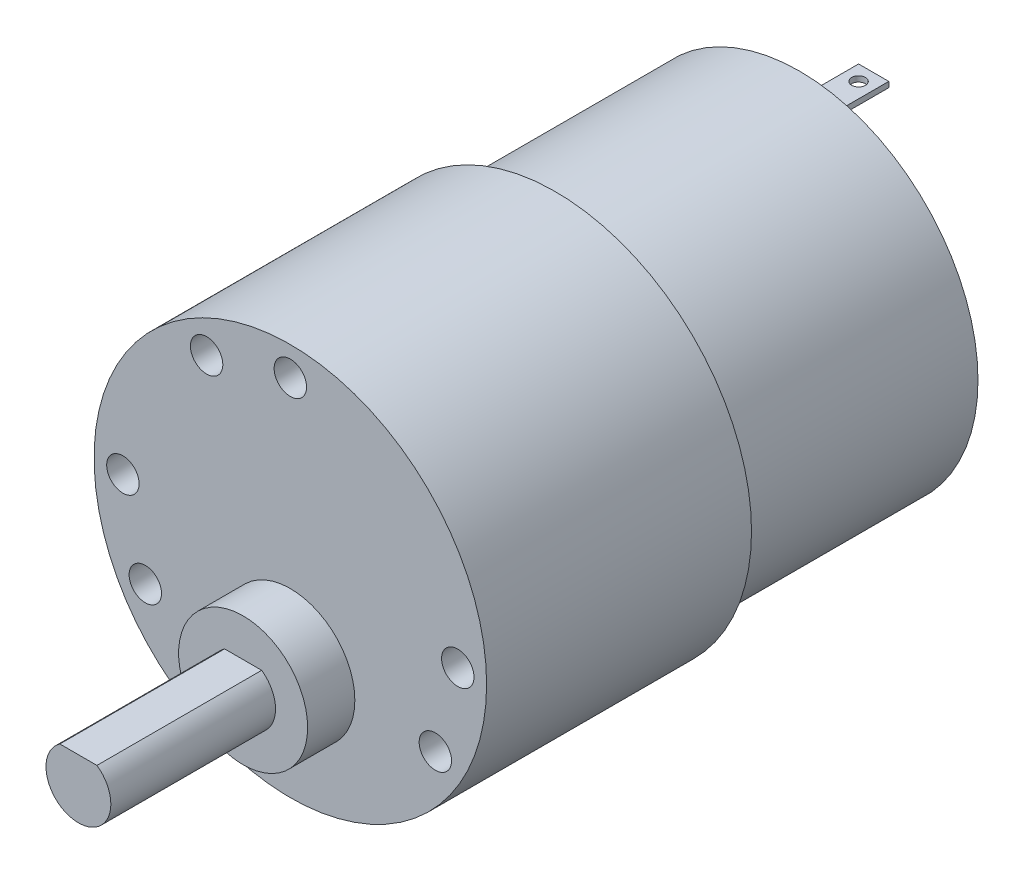
SolidWorks part; units mm, degrees
ref_plane "Front Plane" through (0, 0, 0) normal (0, 0, 1) x (1, 0, 0)
ref_plane "Top Plane" through (0, 0, 0) normal (0, 1, 0) x (1, 0, 0)
ref_plane "Right Plane" through (0, 0, 0) normal (1, 0, 0) x (0, 0, -1)
sketch "Sketch1" plane through (0, 0, 0) normal (0, 0, 1) x (1, 0, 0)
  circle A0 centre (0, 0) radius 18.161
  dimension "D1" = 36.322
extrude "Boss-Extrude1" add sketch "Sketch1" along normal blind 24.511
sketch "Sketch2" plane through (0, 0, 0) normal (0, 0, -1) x (-1, 0, 0)
  circle A0 centre (0, 0) radius 16.51
  dimension "D1" = 33.02
extrude "Boss-Extrude2" add sketch "Sketch2" along normal blind 22.606
sketch "Sketch3" plane through (0, 0, -22.606) normal (0, 0, -1) x (-1, 0, 0)
  circle A0 centre (0, 0) radius 4.5085
  dimension "D1" = 9.017
extrude "Boss-Extrude3" add sketch "Sketch3" along normal blind 3.302
sketch "Sketch4" plane through (0, 0, -22.606) normal (0, 0, -1) x (-1, 0, 0)
  circle A0 centre (0, -12.7) radius 2.413
  circle A1 centre (0, 12.7) radius 2.413
  circle A2 centre (0, 0) radius 18.161 construction
  dimension "D1" = 4.826
  dimension "D2" = 4.826
  dimension "D3" = 12.7
  dimension "D4" = 12.7
extrude "Boss-Extrude4" add sketch "Sketch4" along normal blind 1.27
sketch "Sketch5" plane through (0, 0, 24.511) normal (0, 0, 1) x (1, 0, 0)
  circle A0 centre (0, -7.366) radius 5.969
  dimension "D1" = 11.938
  dimension "D2" = 7.366
extrude "Boss-Extrude5" add sketch "Sketch5" along normal blind 4.3688
sketch "Sketch6" plane through (0, 0, 28.8798) normal (0, 0, 1) x (1, 0, 0)
  line L0 (-1.7157, -4.905) -> (1.7157, -4.905)
  arc A0 (-1.7157, -4.905) -> (1.7157, -4.905) centre (0, -7.366) ccw
  dimension "D1" = 6
  dimension "D2" = 2.461
extrude "Boss-Extrude6" add sketch "Sketch6" along normal blind 15.24
ref_axis "Axis2" through (0, 12.7, -23.876) along (0, 0, 1)
ref_axis "Axis3" through (0, -12.7, -23.876) along (0, 0, 1)
ref_plane "Plane1" through (0, 0, 0) normal (1, 0, 0) x (0, 0, -1)
ref_plane "Plane2" through (0, 12.7, 0) normal (0, 1, 0) x (0, 0, 1)
ref_plane "Plane3" through (0, -12.7, 0) normal (0, 1, 0) x (0, 0, 1)
sketch "Sketch8" plane through (0, 12.7, 0) normal (0, 1, 0) x (0, 0, 1)
  line L0 (-23.876, 2.413) -> (-23.876, -2.413) construction
  line L1 (-23.876, 1.397) -> (-29.464, 1.397)
  line L2 (-23.876, 1.397) -> (-23.876, -1.397)
  line L3 (-23.876, -1.397) -> (-29.464, -1.397)
  line L4 (-29.464, 1.397) -> (-29.464, -1.397)
  line L5 (0.6985, 0) -> (-0.6985, 0) construction
  circle A0 centre (-28.067, 0) radius 0.635
  dimension "D4" = 1.27
  dimension "D1" = 2.794
  dimension "D2" = 1.397
  dimension "D3" = 5.588
  dimension "D5" = 1.397
extrude "Boss-Extrude7" add sketch "Sketch8" along normal mid plane 0.508
pattern_circular "CirPattern1" count 2 over 360 about axis through (0, 0, -25.908) along (0, 0, 1) of "Boss-Extrude7"
sketch "Sketch9" plane through (0, 0, 24.511) normal (0, 0, 1) x (1, 0, 0)
  line L0 (0, 0) -> (0, 15.494) construction
  circle A0 centre (0, 0) radius 15.494 construction
  dimension "D1" = 30.988
hole_wizard "Ø3.0mm Dowel Hole1" positions "Sketch11" profile "Sketch12" hole size "Ø3.0" standard "ANSI Metric"
sketch "Sketch11" plane through (0, 0, 24.511) normal (0, 0, 1) x (1, 0, 0)
  point P0 (0, 15.494)
sketch "Sketch12" plane through (0, 15.494, 24.511) normal (1, 0, 0) x (0, -1, 0)
  line L0 (0, 0) -> (0, 11.0613)
  line L1 (0, 11.0613) -> (1.5, 10.16)
  line L2 (1.5, 10.16) -> (1.5, 0)
  line L5 (1.5, 0) -> (0, 0)
  line L10 (0, 11.0613) -> (-1.5, 10.16) construction
  line L11 (0, -6.35) -> (0, 107.95) construction
  dimension "Hole Dia." = 3
  dimension "Hole Depth" = 10.16
  dimension "Drill Angle" = 118
pattern_circular "CirPattern2" count 12 over 360 about axis through (0, 0, 24.511) along (0, 0, -1) skipping 1, 2, 5, 6, 10 of "Ø3.0mm Dowel Hole1"
